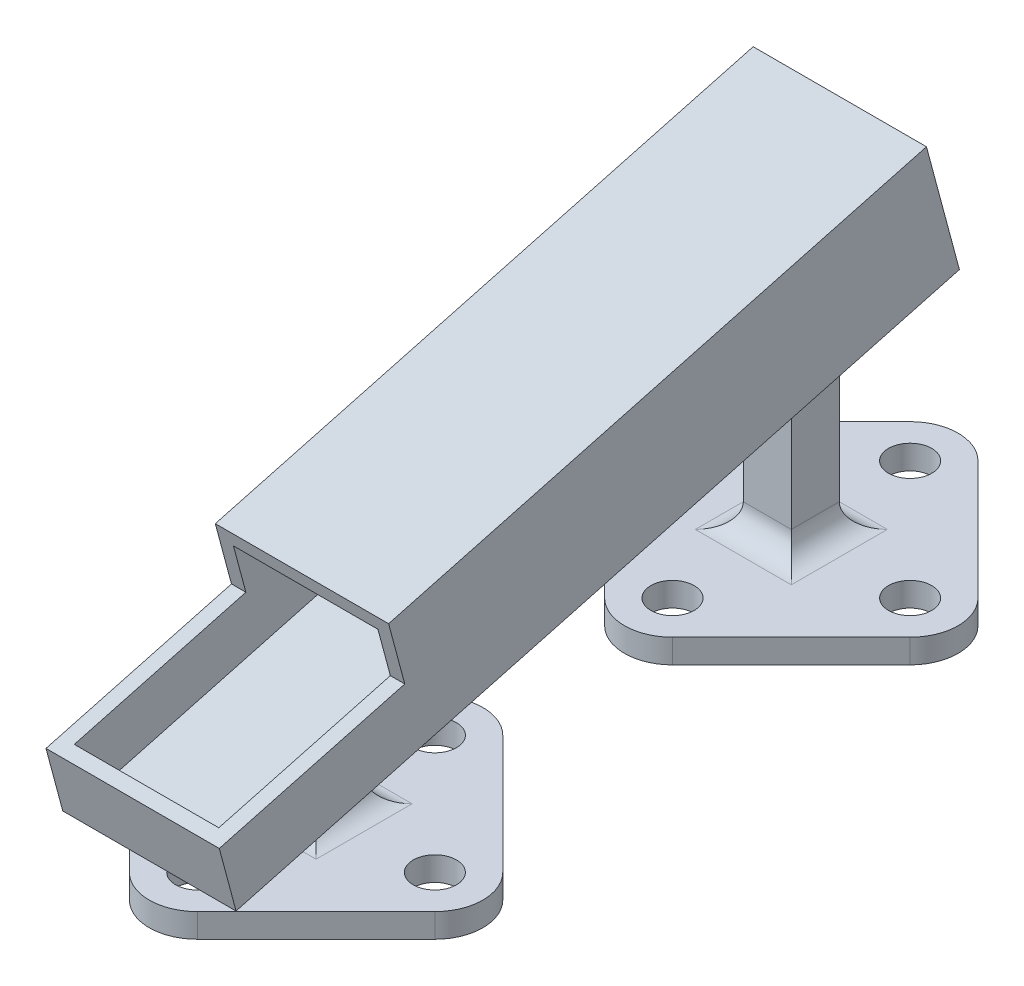
SolidWorks part; units mm, degrees
ref_plane "Front" through (0, 0, 0) normal (0, 0, 1) x (1, 0, 0)
ref_plane "Top" through (0, 0, 0) normal (0, 1, 0) x (1, 0, 0)
ref_plane "Right" through (0, 0, 0) normal (1, 0, 0) x (0, 0, -1)
ref_axis "Axis1" through (0, 55, 0) along (0, -1, 0)
ref_axis "Axis2" through (88.99, 0, 0) along (-1, 0, 0)
ref_axis "Axis3" through (0, 0, 55) along (0, 0, -1)
sketch "Sketch1" plane through (0, 0, 0) normal (0, 1, 0) x (1, 0, 0)
  line L0 (-24.75, 0) -> (0, 24.75) construction
  line L9 (-24.75, 0) -> (0, -24.75) construction
  line L11 (0, 24.75) -> (24.75, 0) construction
  line L12 (0, -24.75) -> (24.75, 0) construction
  line L13 (-24.75, 0) -> (24.75, 0) construction
  line L14 (0, 24.75) -> (0, -24.75) construction
  line L15 (-31.8211, 7.0711) -> (-7.0711, 31.8211)
  line L16 (7.0711, 31.8211) -> (31.8211, 7.0711)
  line L17 (7.0711, -31.8211) -> (31.8211, -7.0711)
  line L18 (-31.8211, -7.0711) -> (-7.0711, -31.8211)
  line L19 (0, -38.8921) -> (38.8921, 0) construction
  line L20 (-38.8921, 0) -> (0, -38.8921) construction
  line L21 (0, 38.8921) -> (38.8921, 0) construction
  line L22 (-38.8921, 0) -> (0, 38.8921) construction
  arc A4 (7.0711, -31.8211) -> (-7.0711, -31.8211) centre (0, -24.75) cw
  arc A5 (31.8211, 7.0711) -> (31.8211, -7.0711) centre (24.75, 0) cw
  arc A6 (-7.0711, 31.8211) -> (7.0711, 31.8211) centre (0, 24.75) cw
  arc A7 (-31.8211, 7.0711) -> (-31.8211, -7.0711) centre (-24.75, 0) ccw
  circle A8 centre (0, 24.75) radius 4.5
  circle A9 centre (24.75, 0) radius 4.5
  circle A10 centre (0, -24.75) radius 4.5
  circle A11 centre (-24.75, 0) radius 4.5
  point P1 (0, 0)
  dimension "D3" = 10
  dimension "D4" = 9
  dimension "D1" = 49.5
  dimension "D2" = 10
extrude "Boss-Extrude1" add sketch "Sketch1" along normal mid plane 5
ref_plane "Plane1" through (0, 0, 49.5) normal (0, 0, 1) x (1, 0, 0)
mirror "Mirror3" about plane through (0, 0, 49.5) normal (0, 0, 1) of bodies 101
sketch "Sketch2" plane through (0, 0, 0) normal (1, 0, 0) x (0, 0, -1)
  line L0 (-106.0711, 2.5) -> (-130.8211, 2.5) construction
  line L1 (-104, 2.5) -> (-94, 2.5)
  line L2 (-104, 2.5) -> (-104, 47.5)
  line L3 (-104, 47.5) -> (-94, 47.5)
  line L4 (-94, 2.5) -> (-94, 47.5)
  line L5 (-106.0711, -2.5) -> (-91.9289, -2.5) construction
  line L6 (-67.1789, -2.5) -> (-91.9289, -2.5) construction
  point P8 (-99, -2.5)
  point P9 (-99, 47.5)
  dimension "D1" = 10
  dimension "D2" = 50
extrude "Boss-Extrude2" add sketch "Sketch2" along normal mid plane 10 separate body
mirror "Mirror5" about plane through (0, 0, 49.5) normal (0, 0, 1) of bodies 103
sketch "Sketch3" plane through (0, 0, 0) normal (1, 0, 0) x (0, 0, -1)
  line L0 (-104, 17.5) -> (5, 46.7065)
  line L1 (-67.1789, -2.5) -> (-91.9289, -2.5) construction
  line L2 (-104, 47.5) -> (-104, 2.5) construction
  line L3 (-106.0711, 2.5) -> (-130.8211, 2.5) construction
  line L4 (5, 47.5) -> (5, 2.5) construction
  point P6 (-104, 17.5)
  dimension "D1" = 15
  dimension "D2" = 15
extrude "Cut-Extrude1" cut sketch "Sketch3" against normal through all both and the other way through all
sketch "Sketch4" plane through (0, 0, 0) normal (1, 0, 0) x (0, 0, -1)
  line L0 (-130.8211, 10.3133) -> (14.0678, 49.1362)
  line L1 (-130.8211, 10.3133) -> (-131.3387, 12.2452)
  line L2 (14.0678, 49.1362) -> (13.5502, 51.068)
  line L3 (-131.3387, 12.2452) -> (13.5502, 51.068)
  line L6 (-104, 17.5) -> (-94, 20.1795) construction
  dimension "D1" = 2
  dimension "D2" = 150
extrude "Boss-Extrude3" add sketch "Sketch4" along normal mid plane 30.1 separate body
combine bodies "Combine1" operation type add bodies to combine 102 106
combine bodies "Combine2" operation type add bodies to combine 107 101
fillet "Fillet1" radius 5 4 edges at (0, 2.5, 94) (-5, 2.5, 99) (0, 2.5, 104) (5, 2.5, 99)
fillet "Fillet2" radius 5 4 edges at (0, 2.5, 5) (0, 2.5, -5) (-5, 2.5, 0) (5, 2.5, 0)
sketch "Sketch5" plane through (0, 44.2596, 11.8593) normal (0, 0.9659, 0.2588) x (1, 0, 0)
  line L0 (15.05, -108.6442) -> (0, -108.6442) construction
  line L1 (15.05, 26.3058) -> (15.05, -123.6942) construction
  line L2 (0, -108.6442) -> (0, -123.6942) construction
  line L3 (15.05, -123.6942) -> (-15.05, -123.6942) construction
  line L4 (-11.83, -108.6442) -> (-15.05, -123.6942)
  line L5 (-15.05, -123.6942) -> (0, -123.6942)
  line L6 (0, -123.6942) -> (15.05, -123.6942)
  line L7 (15.05, -123.6942) -> (15.05, -108.6442)
  circle A0 centre (0, -108.6442) radius 8.73 construction
  circle A1 centre (0, -108.6442) radius 8.83
  circle A2 centre (0, -108.6442) radius 11.83
  dimension "D1" = 17.46
  dimension "D2" = 0.1
  dimension "D3" = 3
sketch "Sketch6" plane through (0, 44.2596, 11.8593) normal (0, 0.9659, 0.2588) x (1, 0, 0)
  line L4 (-15.05, 26.3058) -> (-15.05, -123.6942)
  line L5 (-15.05, -123.6942) -> (15.05, -123.6942)
  line L6 (15.05, -123.6942) -> (15.05, 26.3058)
  line L7 (15.05, 26.3058) -> (-15.05, 26.3058)
  line L8 (-15.05, 26.3058) -> (-15.05, -123.6942)
  line L9 (-15.05, -123.6942) -> (15.05, -123.6942)
  line L10 (15.05, -123.6942) -> (15.05, 26.3058)
  line L11 (15.05, 26.3058) -> (-15.05, 26.3058)
  line L16 (-18.05, 29.3058) -> (-18.05, -126.6942)
  line L17 (-18.05, -126.6942) -> (18.05, -126.6942)
  line L18 (18.05, -126.6942) -> (18.05, 29.3058)
  line L19 (18.05, 29.3058) -> (-18.05, 29.3058)
  line L20 (-18.05, 29.3058) -> (-18.05, -126.6942)
  line L21 (-18.05, -126.6942) -> (18.05, -126.6942)
  line L22 (18.05, -126.6942) -> (18.05, 29.3058)
  line L23 (18.05, 29.3058) -> (-18.05, 29.3058)
  dimension "D1" = 0
  dimension "D2" = 3
extrude "Boss-Extrude4" add sketch "Sketch6" against normal up to vertex (2 mm away) and the other way blind 16.5 up to point (15.05, 49.1362, -14.0678)
sketch "Sketch7" plane through (0, 60.1974, 16.1298) normal (0, 0.9659, 0.2588) x (1, 0, 0)
  line L0 (15.05, 26.3058) -> (15.05, -123.6942) construction
  line L1 (15.05, 26.3058) -> (15.05, -86.6942)
  line L3 (-15.05, 26.3058) -> (-15.05, -123.6942) construction
  line L4 (18.05, 29.3058) -> (-18.05, 29.3058)
  line L5 (-18.05, 29.3058) -> (-18.05, -126.6942)
  line L6 (-18.05, -126.6942) -> (18.05, -126.6942)
  line L7 (18.05, -126.6942) -> (18.05, 29.3058)
  line L8 (18.05, 29.3058) -> (-18.05, 29.3058)
  line L9 (-18.05, 29.3058) -> (-18.05, -86.6942)
  line L11 (18.05, -86.6942) -> (18.05, 29.3058)
  line L12 (15.05, 26.3058) -> (-15.05, 26.3058) construction
  line L14 (-15.05, 26.3058) -> (-15.05, -86.6942)
  line L15 (15.05, 26.3058) -> (-15.05, 26.3058)
  line L16 (18.05, -86.6942) -> (15.05, -86.6942)
  line L17 (-15.05, -86.6942) -> (-18.05, -86.6942)
  line L18 (-18.05, -126.6942) -> (18.05, -126.6942) construction
  dimension "D2" = 40
  dimension "D1" = 0
extrude "Boss-Extrude5" add sketch "Sketch7" along normal blind 5
sketch "Sketch8" plane through (0, 65.027, 17.4239) normal (0, 0.9659, 0.2588) x (1, 0, 0)
  line L0 (-18.05, 29.3058) -> (-18.05, -86.6942) construction
  line L1 (-18.05, -86.6942) -> (18.05, -86.6942)
  line L2 (-18.05, -86.6942) -> (-18.05, 29.3058)
  line L3 (-18.05, 29.3058) -> (18.05, 29.3058)
  line L4 (18.05, -86.6942) -> (18.05, 29.3058)
extrude "Boss-Extrude6" add sketch "Sketch8" along normal blind 3
sketch "Sketch10" plane through (0, 6.8085, -25.4095) normal (0, -0.2588, 0.9659) x (1, 0, 0)
  line L4 (-15.05, 45.8209) -> (15.05, 45.8209)
  line L5 (15.05, 45.8209) -> (15.05, 67.3209)
  line L6 (15.05, 67.3209) -> (-15.05, 67.3209)
  line L7 (-15.05, 67.3209) -> (-15.05, 45.8209)
  line L8 (-15.05, 45.8209) -> (15.05, 45.8209)
  line L9 (15.05, 45.8209) -> (15.05, 67.3209)
  line L10 (15.05, 67.3209) -> (-15.05, 67.3209)
  line L11 (-15.05, 67.3209) -> (-15.05, 45.8209)
  dimension "D1" = 0
extrude "Cut-Extrude2" cut sketch "Sketch10" against normal up to next
sketch "Sketch11" plane through (0, 60.1974, 16.1298) normal (0, 0.9659, 0.2588) x (1, 0, 0)
  line L1 (-18.05, -126.6942) -> (18.05, -126.6942)
  line L2 (-18.05, -126.6942) -> (-18.05, -86.6942)
  line L3 (-18.05, -86.6942) -> (18.05, -86.6942)
  line L4 (18.05, -126.6942) -> (18.05, -86.6942)
extrude "Cut-Extrude3" cut sketch "Sketch11" against normal blind 5
